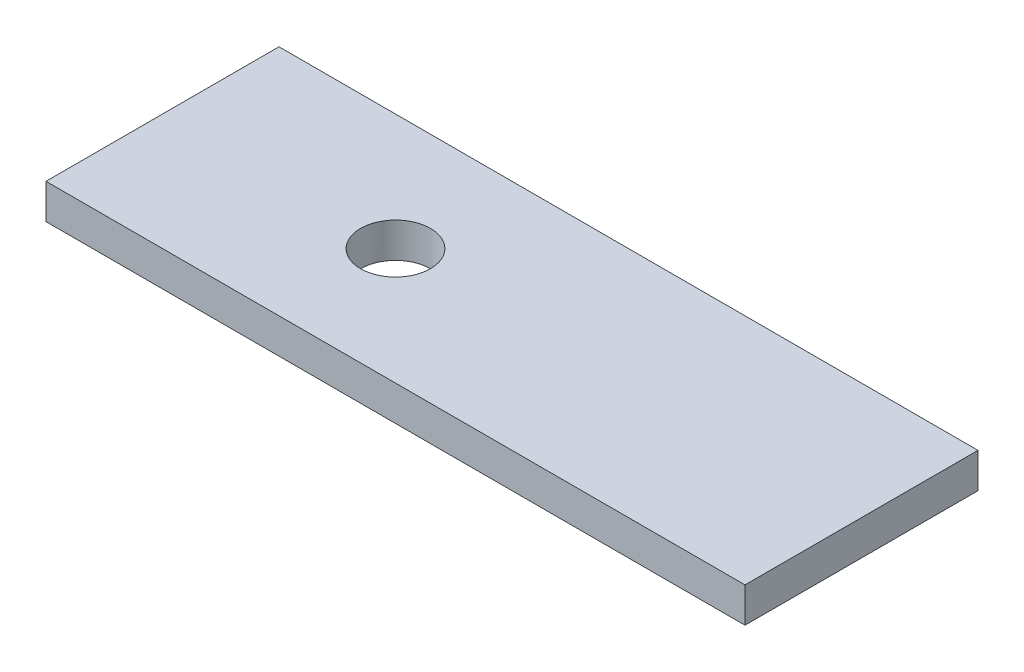
SolidWorks part; units mm, degrees
ref_plane "Front Plane" through (0, 0, 0) normal (0, 0, 1) x (1, 0, 0)
ref_plane "Top Plane" through (0, 0, 0) normal (0, 1, 0) x (1, 0, 0)
ref_plane "Right Plane" through (0, 0, 0) normal (1, 0, 0) x (0, 0, -1)
sketch "Sketch1" plane through (0, 0, 0) normal (0, 1, 0) x (1, 0, 0)
  line L1 (0, 0) -> (30, 0)
  line L2 (0, 0) -> (0, 10)
  line L3 (0, 10) -> (30, 10)
  line L4 (30, 0) -> (30, 10)
  dimension "D1" = 10
  dimension "D2" = 30
base flange "Base-Flange1" sketch "Sketch1" thickness 1.5 reverse thickness direction no parameters "D1"=0.7366
hole_wizard "Ø3.0mm Press Dowel Hole1" positions "Sketch6" profile "Sketch7" hole size "Ø3.0" standard "ANSI Metric" end condition up to next
sketch "Sketch6" plane through (0, 0, 0) normal (0, 1, 0) x (1, 0, 0)
  line L0 (0, 10) -> (0, 0) construction
  point P0 (10, 5)
  point P5 (0, 5)
  dimension "D1" = 10
sketch "Sketch7" plane through (10, 0, -5) normal (1, 0, 0) x (0, 0, 1)
  line L0 (0, 0) -> (0, 1.5)
  line L1 (0, 1.5) -> (1.5, 1.5)
  line L2 (1.5, 1.5) -> (1.5, 0)
  line L5 (1.5, 0) -> (0, 0)
  line L11 (0, -6.35) -> (0, 107.95) construction
  dimension "Thru Hole Dia." = 3
  dimension "Thru Hole Depth" = 1.5
sketch "Bend-Lines1" [suppressed] plane through (0, 0, 0) normal (0, 1, 0) x (1, 0, 0)
sketch "Bounding-Box1" [suppressed] plane through (0, 0, 0) normal (0, 1, 0) x (1, 0, 0)
sheet metal parameters "Sheet-Metal1" thickness 1.5 parameters "D1"=0.7366
flat pattern "Flat-Pattern1" [suppressed]
sketch "Bend-Lines2" plane through (0, 0, 0) normal (0, 1, 0) x (1, 0, 0)
sketch3d "Bounding-Box2" [suppressed]
  line L0 (-30, 10, 0) -> (0, 10, 0) construction
  line L1 (-30, 0, 0) -> (0, 0, 0) construction
  line L2 (-30, 10, 0) -> (-30, 0, 0) construction
  line L3 (0, 10, 0) -> (0, 0, 0) construction
sheet metal parameters "Sheet-Metal2" thickness 1.5 parameters "D1"=0.7366
flat pattern "Flat-Pattern1"
sketch "Bend-Lines2" plane through (0, 0, 0) normal (0, 1, 0) x (1, 0, 0)
sketch3d "Bounding-Box2" [suppressed]
  line L0 (30, 10, 0) -> (0, 10, 0) construction
  line L1 (30, 0, 0) -> (0, 0, 0) construction
  line L2 (30, 10, 0) -> (30, 0, 0) construction
  line L3 (0, 10, 0) -> (0, 0, 0) construction
